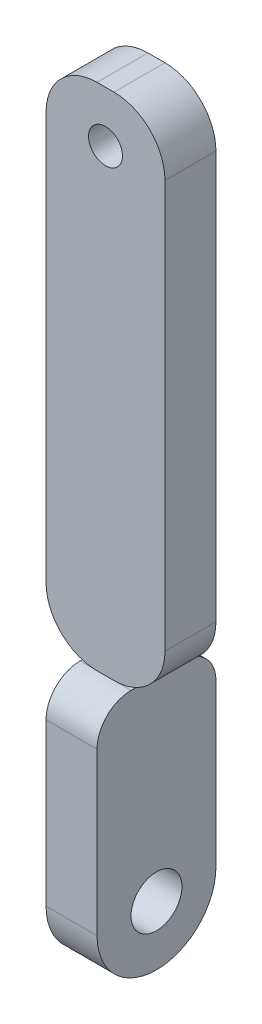
SolidWorks part; units mm, degrees
ref_plane "Front Plane" through (0, 0, 0) normal (0, 0, 1) x (1, 0, 0)
ref_plane "Top Plane" through (0, 0, 0) normal (0, 1, 0) x (1, 0, 0)
ref_plane "Right Plane" through (0, 0, 0) normal (1, 0, 0) x (0, 0, -1)
sketch "Sketch1" plane through (0, 0, 0) normal (0, 0, 1) x (1, 0, 0)
  line L1 (3, 0) -> (4, 0)
  line L2 (0, -3) -> (0, -27)
  line L3 (3, -30) -> (4, -30)
  line L4 (7, -3) -> (7, -27)
  line L5 (2, -30) -> (5, -30)
  line L6 (2, -30) -> (2, -45)
  line L7 (2, -45) -> (5, -45)
  line L8 (5, -30) -> (5, -45)
  arc A0 (4, 0) -> (7, -3) centre (4, -3) cw
  arc A1 (0, -27) -> (3, -30) centre (3, -27) ccw
  arc A2 (4, -30) -> (7, -27) centre (4, -27) ccw
  arc A3 (3, 0) -> (0, -3) centre (3, -3) ccw
  circle A4 centre (3.5, -3) radius 1
  point P11 (7, 0)
  point P16 (7, -30)
  point P19 (0, 0)
  dimension "D6" = 3
  dimension "D7" = 2
  dimension "D1" = 30
  dimension "D2" = 15
  dimension "D3" = 7
  dimension "D4" = 3
  dimension "D5" = 2
  dimension "D8" = 3
  dimension "D9" = 3.5
extrude "Boss-Extrude1" add sketch "Sketch1" along normal mid plane 3 contours L1 A3 L2 A1 L3 A2 L4 A0 A4 region at (3.5, -15.1893, 0)
extrude "Boss-Extrude2" add sketch "Sketch1<3>" along normal mid plane 7 contours L8 L5 L3 L6 L7 region at (3.5, -37.5, 0)
sketch "Sketch1<3>" plane through (0, 0, 0) normal (0, 0, 1) x (1, 0, 0) same geometry as "Sketch1"
fillet "Fillet1" radius 2 1 edges at (3.5, -30, 3.5)
fillet "Fillet2" radius 2 1 edges at (3.5, -30, -3.5)
fillet "Fillet4" radius 3.5 2 edges at (3.5, -45, 3.5) (3.5, -45, -3.5)
sketch "Sketch2" plane through (5, 0, 0) normal (1, 0, 0) x (0, 0, -1)
  circle A0 centre (0, -41.5) radius 1.5
  arc A1 (0, -45) -> (3.5, -41.5) centre (0, -41.5) ccw construction
  dimension "D1" = 3
extrude "Cut-Extrude1" cut sketch "Sketch2" against normal blind 7
